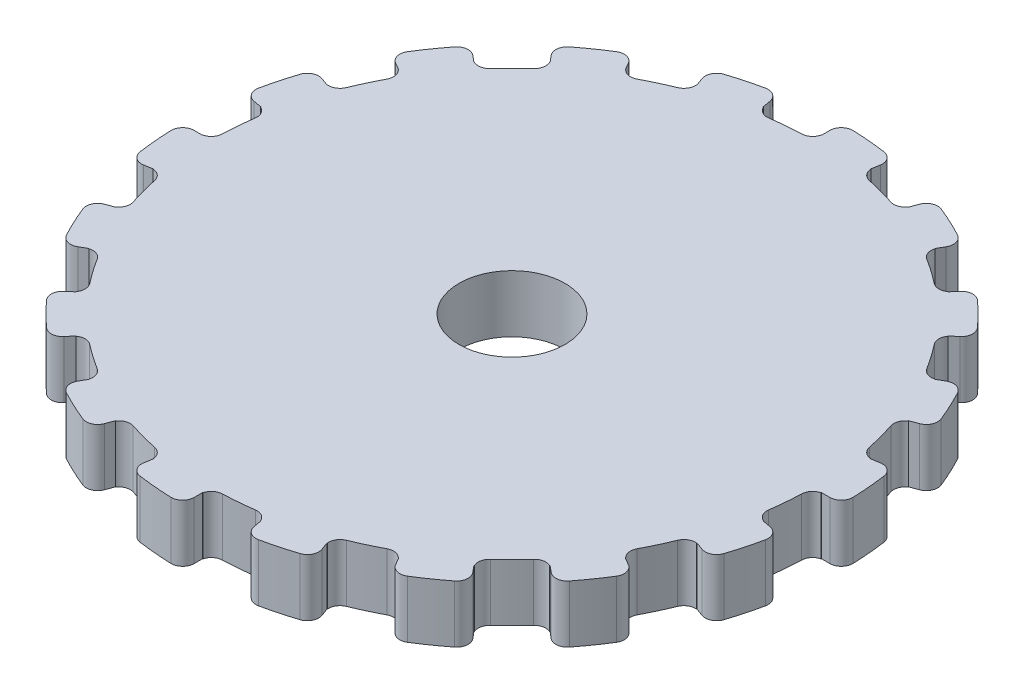
SolidWorks part; units mm, degrees
material "PLA"
ref_plane "Alzado" through (0, 0, 0) normal (0, 0, 1) x (1, 0, 0)
ref_plane "Planta" through (0, 0, 0) normal (0, 1, 0) x (1, 0, 0)
ref_plane "Vista lateral" through (0, 0, 0) normal (1, 0, 0) x (0, 0, -1)
sketch "Croquis1" plane through (0, 0, 0) normal (0, 1, 0) x (1, 0, 0)
  line L0 (0, 0) -> (0, 24) construction
  line L1 (0, 0) -> (4.1676, 23.6354) construction
  line L2 (0, 0) -> (8.2085, 22.5526) construction
  line L3 (0, 0) -> (12, 20.7846) construction
  line L4 (0, 0) -> (15.4269, 18.3851) construction
  line L5 (0, 0) -> (18.3851, 15.4269) construction
  line L6 (0, 0) -> (20.7846, 12) construction
  line L7 (0, 0) -> (22.5526, 8.2085) construction
  line L8 (0, 0) -> (23.6354, 4.1676) construction
  line L9 (0, 0) -> (24, 0) construction
  line L10 (0, 0) -> (23.6354, -4.1676) construction
  line L11 (0, 0) -> (22.5526, -8.2085) construction
  line L12 (0, 0) -> (20.7846, -12) construction
  line L13 (0, 0) -> (18.3851, -15.4269) construction
  line L14 (0, 0) -> (15.4269, -18.3851) construction
  line L15 (0, 0) -> (12, -20.7846) construction
  line L16 (0, 0) -> (8.2085, -22.5526) construction
  line L17 (0, 0) -> (4.1676, -23.6354) construction
  line L18 (0, 0) -> (0, -24) construction
  line L19 (0, 0) -> (-4.1676, -23.6354) construction
  line L20 (0, 0) -> (-8.2085, -22.5526) construction
  line L21 (0, 0) -> (-12, -20.7846) construction
  line L22 (0, 0) -> (-15.4269, -18.3851) construction
  line L23 (0, 0) -> (-18.3851, -15.4269) construction
  line L24 (0, 0) -> (-20.7846, -12) construction
  line L25 (0, 0) -> (-22.5526, -8.2085) construction
  line L26 (0, 0) -> (-23.6354, -4.1676) construction
  line L27 (0, 0) -> (-24, 0) construction
  line L28 (0, 0) -> (-23.6354, 4.1676) construction
  line L29 (0, 0) -> (-22.5526, 8.2085) construction
  line L30 (0, 0) -> (-20.7846, 12) construction
  line L31 (0, 0) -> (-18.3851, 15.4269) construction
  line L32 (0, 0) -> (-15.4269, 18.3851) construction
  line L33 (0, 0) -> (-12, 20.7846) construction
  line L34 (0, 0) -> (-8.2085, 22.5526) construction
  line L35 (0, 0) -> (-4.1676, 23.6354) construction
  line L36 (4.1676, 23.6354) -> (3.7508, 21.2718)
  line L37 (7.3876, 20.2974) -> (8.2085, 22.5526)
  line L38 (12, 20.7846) -> (10.8, 18.7061)
  line L39 (13.8842, 16.5466) -> (15.4269, 18.3851)
  line L40 (18.3851, 15.4269) -> (16.5466, 13.8842)
  line L41 (18.7061, 10.8) -> (20.7846, 12)
  line L42 (22.5526, 8.2085) -> (20.2974, 7.3876)
  line L43 (21.2718, 3.7508) -> (23.6354, 4.1676)
  line L44 (24, 0) -> (21.6, 0)
  line L45 (21.2718, -3.7508) -> (23.6354, -4.1676)
  line L46 (22.5526, -8.2085) -> (20.2974, -7.3876)
  line L47 (18.7061, -10.8) -> (20.7846, -12)
  line L48 (18.3851, -15.4269) -> (16.5466, -13.8842)
  line L49 (13.8842, -16.5466) -> (15.4269, -18.3851)
  line L50 (12, -20.7846) -> (10.8, -18.7061)
  line L51 (7.3876, -20.2974) -> (8.2085, -22.5526)
  line L52 (4.1676, -23.6354) -> (3.7508, -21.2718)
  line L53 (0, -21.6) -> (0, -24)
  line L54 (-4.1676, -23.6354) -> (-3.7508, -21.2718)
  line L55 (-7.3876, -20.2974) -> (-8.2085, -22.5526)
  line L56 (-12, -20.7846) -> (-10.8, -18.7061)
  line L57 (-13.8842, -16.5466) -> (-15.4269, -18.3851)
  line L58 (-18.3851, -15.4269) -> (-16.5466, -13.8842)
  line L59 (-18.7061, -10.8) -> (-20.7846, -12)
  line L60 (-22.5526, -8.2085) -> (-20.2974, -7.3876)
  line L61 (-21.2718, -3.7508) -> (-23.6354, -4.1676)
  line L62 (-24, 0) -> (-21.6, 0)
  line L63 (-21.2718, 3.7508) -> (-23.6354, 4.1676)
  line L64 (-22.5526, 8.2085) -> (-20.2974, 7.3876)
  line L65 (-18.7061, 10.8) -> (-20.7846, 12)
  line L66 (-18.3851, 15.4269) -> (-16.5466, 13.8842)
  line L67 (-13.8842, 16.5466) -> (-15.4269, 18.3851)
  line L68 (-12, 20.7846) -> (-10.8, 18.7061)
  line L69 (-7.3876, 20.2974) -> (-8.2085, 22.5526)
  line L70 (-4.1676, 23.6354) -> (-3.7508, 21.2718)
  line L71 (0, 21.6) -> (0, 24)
  circle A1 centre (0, 0) radius 3.7
  arc A2 (0, 24) -> (4.1676, 23.6354) centre (0, 0) cw
  arc A4 (3.7508, 21.2718) -> (7.3876, 20.2974) centre (0, 0) cw
  arc A5 (8.2085, 22.5526) -> (12, 20.7846) centre (0, 0) cw
  arc A6 (10.8, 18.7061) -> (13.8842, 16.5466) centre (0, 0) cw
  arc A7 (15.4269, 18.3851) -> (18.3851, 15.4269) centre (0, 0) cw
  arc A8 (16.5466, 13.8842) -> (18.7061, 10.8) centre (0, 0) cw
  arc A9 (20.7846, 12) -> (22.5526, 8.2085) centre (0, 0) cw
  arc A10 (20.2974, 7.3876) -> (21.2718, 3.7508) centre (0, 0) cw
  arc A11 (23.6354, 4.1676) -> (24, 0) centre (0, 0) cw
  arc A12 (21.6, 0) -> (21.2718, -3.7508) centre (0, 0) cw
  arc A13 (23.6354, -4.1676) -> (22.5526, -8.2085) centre (0, 0) cw
  arc A14 (20.2974, -7.3876) -> (18.7061, -10.8) centre (0, 0) cw
  arc A15 (20.7846, -12) -> (18.3851, -15.4269) centre (0, 0) cw
  arc A16 (16.5466, -13.8842) -> (13.8842, -16.5466) centre (0, 0) cw
  arc A17 (15.4269, -18.3851) -> (12, -20.7846) centre (0, 0) cw
  arc A18 (10.8, -18.7061) -> (7.3876, -20.2974) centre (0, 0) cw
  arc A19 (8.2085, -22.5526) -> (4.1676, -23.6354) centre (0, 0) cw
  arc A20 (3.7508, -21.2718) -> (0, -21.6) centre (0, 0) cw
  arc A21 (0, -24) -> (-4.1676, -23.6354) centre (0, 0) cw
  arc A22 (-3.7508, -21.2718) -> (-7.3876, -20.2974) centre (0, 0) cw
  arc A23 (-8.2085, -22.5526) -> (-12, -20.7846) centre (0, 0) cw
  arc A24 (-10.8, -18.7061) -> (-13.8842, -16.5466) centre (0, 0) cw
  arc A25 (-15.4269, -18.3851) -> (-18.3851, -15.4269) centre (0, 0) cw
  arc A26 (-16.5466, -13.8842) -> (-18.7061, -10.8) centre (0, 0) cw
  arc A27 (-20.7846, -12) -> (-22.5526, -8.2085) centre (0, 0) cw
  arc A28 (-20.2974, -7.3876) -> (-21.2718, -3.7508) centre (0, 0) cw
  arc A29 (-23.6354, -4.1676) -> (-24, 0) centre (0, 0) cw
  arc A30 (-21.6, 0) -> (-21.2718, 3.7508) centre (0, 0) cw
  arc A31 (-23.6354, 4.1676) -> (-22.5526, 8.2085) centre (0, 0) cw
  arc A32 (-20.2974, 7.3876) -> (-18.7061, 10.8) centre (0, 0) cw
  arc A33 (-20.7846, 12) -> (-18.3851, 15.4269) centre (0, 0) cw
  arc A34 (-16.5466, 13.8842) -> (-13.8842, 16.5466) centre (0, 0) cw
  arc A35 (-15.4269, 18.3851) -> (-12, 20.7846) centre (0, 0) cw
  arc A36 (-10.8, 18.7061) -> (-7.3876, 20.2974) centre (0, 0) cw
  arc A37 (-8.2085, 22.5526) -> (-4.1676, 23.6354) centre (0, 0) cw
  arc A38 (-3.7508, 21.2718) -> (0, 21.6) centre (0, 0) cw
  point P44 (0, 0)
  point P131 (0, 0)
  dimension "D1" = 10
  dimension "D3" = 18
  dimension "D2" = 18
extrude "Saliente-Extruir1" add sketch "Croquis1" along normal blind 4 contours A38 L70 A37 L69 A36 L68 A35 L67 A34 L66 A33 L65 A32 L64 A31 L63 A30 L62 A29 L61 A28 L60 A27 L59 A26 L58 A25 L57 A24 L56 A23 L55 A22 L54 A21 L53 A20 L52 A19 L51 A18 L50 A17 L49 A16 L48 A15 L47 A14 L46 A13 region at (3.2907, 0, -22.5715)
sketch "Croquis2" plane through (0, 4, 0) normal (0, 1, 0) x (1, 0, 0)
  line L0 (0, 1.9) -> (3.1749, 1.9) construction
  line L1 (-2.1, 18.9) -> (2.1, 18.9)
  line L2 (0, 0) -> (0, 1.9) construction
  line L3 (3.1749, 1.9) -> (2.1, 18.9)
  line L4 (0, 18.9) -> (0, 1.9) construction
  line L5 (-3.1749, 1.9) -> (-2.1, 18.9)
  line L6 (-2.178, 0) -> (2.178, 0) construction
  line L7 (3.1749, -1.9) -> (2.1, -18.9)
  line L8 (-2.1, -18.9) -> (2.1, -18.9)
  line L9 (-3.1749, -1.9) -> (-2.1, -18.9)
  circle A0 centre (0, 0) radius 3.7 construction
  arc A1 (3.1749, 1.9) -> (-3.1749, 1.9) centre (0, 0) ccw
  arc A2 (3.1749, -1.9) -> (-3.1749, -1.9) centre (0, 0) cw
sketch "Croquis3" plane through (0, 4, 0) normal (0, 1, 0) x (1, 0, 0)
  line L0 (0, 22.1856) -> (0, 21) construction
  line L1 (3.8525, 21.8485) -> (3.783, 21.4543)
  line L2 (4.1676, 23.6354) -> (3.7508, 21.2718) construction
  line L3 (7.8665, 21.6129) -> (7.451, 20.4715) construction
  line L4 (7.3876, 20.2974) -> (8.2085, 22.5526) construction
  line L5 (7.451, 20.4715) -> (7.5879, 20.8476)
  line L6 (11.0928, 19.2133) -> (10.8927, 18.8666)
  line L7 (14.0033, 16.6885) -> (14.2606, 16.9951)
  line L8 (16.9951, 14.2606) -> (16.6885, 14.0033)
  line L9 (18.8666, 10.8927) -> (19.2133, 11.0928)
  line L10 (20.8476, 7.5879) -> (20.4715, 7.451)
  line L11 (21.4543, 3.783) -> (21.8485, 3.8525)
  line L12 (22.1856, 0) -> (21.7853, 0)
  line L13 (21.4543, -3.783) -> (21.8485, -3.8525)
  line L14 (20.8476, -7.5879) -> (20.4715, -7.451)
  line L15 (18.8666, -10.8927) -> (19.2133, -11.0928)
  line L16 (16.9951, -14.2606) -> (16.6885, -14.0033)
  line L17 (14.0033, -16.6885) -> (14.2606, -16.9951)
  line L18 (11.0928, -19.2133) -> (10.8927, -18.8666)
  line L19 (7.451, -20.4715) -> (7.5879, -20.8476)
  line L20 (3.8525, -21.8485) -> (3.783, -21.4543)
  line L21 (0, -21.7853) -> (0, -22.1856)
  line L22 (-3.8525, -21.8485) -> (-3.783, -21.4543)
  line L23 (-7.451, -20.4715) -> (-7.5879, -20.8476)
  line L24 (-11.0928, -19.2133) -> (-10.8927, -18.8666)
  line L25 (-14.0033, -16.6885) -> (-14.2606, -16.9951)
  line L26 (-16.9951, -14.2606) -> (-16.6885, -14.0033)
  line L27 (-18.8666, -10.8927) -> (-19.2133, -11.0928)
  line L28 (-20.8476, -7.5879) -> (-20.4715, -7.451)
  line L29 (-21.4543, -3.783) -> (-21.8485, -3.8525)
  line L30 (-22.1856, 0) -> (-21.7853, 0)
  line L31 (-21.4543, 3.783) -> (-21.8485, 3.8525)
  line L32 (-20.8476, 7.5879) -> (-20.4715, 7.451)
  line L33 (-18.8666, 10.8927) -> (-19.2133, 11.0928)
  line L34 (-16.9951, 14.2606) -> (-16.6885, 14.0033)
  line L35 (-14.0033, 16.6885) -> (-14.2606, 16.9951)
  line L36 (-11.0928, 19.2133) -> (-10.8927, 18.8666)
  line L37 (-7.451, 20.4715) -> (-7.5879, 20.8476)
  line L38 (-3.8525, 21.8485) -> (-3.783, 21.4543)
  line L39 (0, 21.7853) -> (0, 22.1856)
  line L40 (0, 22.1856) -> (0, 24)
  line L41 (4.1676, 23.6354) -> (3.8525, 21.8485)
  line L42 (7.5879, 20.8476) -> (8.2085, 22.5526)
  line L43 (12, 20.7846) -> (11.0928, 19.2133)
  line L44 (14.2606, 16.9951) -> (15.4269, 18.3851)
  line L45 (18.3851, 15.4269) -> (16.9951, 14.2606)
  line L46 (19.2133, 11.0928) -> (20.7846, 12)
  line L47 (22.5526, 8.2085) -> (20.8476, 7.5879)
  line L48 (21.8485, 3.8525) -> (23.6354, 4.1676)
  line L49 (24, 0) -> (22.1856, 0)
  line L50 (21.8485, -3.8525) -> (23.6354, -4.1676)
  line L51 (22.5526, -8.2085) -> (20.8476, -7.5879)
  line L52 (19.2133, -11.0928) -> (20.7846, -12)
  line L53 (18.3851, -15.4269) -> (16.9951, -14.2606)
  line L54 (14.2606, -16.9951) -> (15.4269, -18.3851)
  line L55 (12, -20.7846) -> (11.0928, -19.2133)
  line L56 (7.5879, -20.8476) -> (8.2085, -22.5526)
  line L57 (4.1676, -23.6354) -> (3.8525, -21.8485)
  line L58 (0, -22.1856) -> (0, -24)
  line L59 (-4.1676, -23.6354) -> (-3.8525, -21.8485)
  line L60 (-7.5879, -20.8476) -> (-8.2085, -22.5526)
  line L61 (-12, -20.7846) -> (-11.0928, -19.2133)
  line L62 (-14.2606, -16.9951) -> (-15.4269, -18.3851)
  line L63 (-18.3851, -15.4269) -> (-16.9951, -14.2606)
  line L64 (-19.2133, -11.0928) -> (-20.7846, -12)
  line L65 (-22.5526, -8.2085) -> (-20.8476, -7.5879)
  line L66 (-21.8485, -3.8525) -> (-23.6354, -4.1676)
  line L67 (-24, 0) -> (-22.1856, 0)
  line L68 (-21.8485, 3.8525) -> (-23.6354, 4.1676)
  line L69 (-22.5526, 8.2085) -> (-20.8476, 7.5879)
  line L70 (-19.2133, 11.0928) -> (-20.7846, 12)
  line L71 (-18.3851, 15.4269) -> (-16.9951, 14.2606)
  line L72 (-14.2606, 16.9951) -> (-15.4269, 18.3851)
  line L73 (-12, 20.7846) -> (-11.0928, 19.2133)
  line L74 (-7.5879, 20.8476) -> (-8.2085, 22.5526)
  line L75 (-4.1676, 23.6354) -> (-3.8525, 21.8485)
  circle A0 centre (0, 0) radius 23 construction
  circle A1 centre (0, 0) radius 21 construction
  arc A2 (0.8288, 22.9851) -> (3.1751, 22.7798) centre (0, 0) cw
  arc A3 (4.4031, 20.5332) -> (6.4534, 19.9838) centre (0, 0) cw
  arc A4 (7.451, 20.4715) -> (6.4534, 19.9838) centre (6.6993, 20.7451) cw
  arc A5 (3.783, 21.4543) -> (4.4031, 20.5332) centre (4.5708, 21.3154) ccw
  arc A6 (3.8525, 21.8485) -> (3.1751, 22.7798) centre (3.0646, 21.9875) ccw
  arc A7 (0, 22.1856) -> (0.8288, 22.9851) centre (0.8, 22.1856) cw
  arc A8 (8.6402, 21.3154) -> (11.506, 19.9151) centre (0, 0) cw construction
  arc A9 (7.5879, 20.8476) -> (8.6402, 21.3154) centre (8.3397, 20.574) cw construction
  arc A10 (7.5879, 20.8476) -> (8.6402, 21.3154) centre (8.3397, 20.574) cw
  arc A11 (8.6402, 21.3154) -> (10.7747, 20.3201) centre (0, 0) cw
  arc A12 (11.0928, 19.2133) -> (10.7747, 20.3201) centre (10.4, 19.6133) ccw
  arc A13 (10.8927, 18.8666) -> (11.1603, 17.789) centre (11.5855, 18.4666) ccw
  arc A14 (11.1603, 17.789) -> (12.8991, 16.5715) centre (0, 0) cw
  arc A15 (14.0033, 16.6885) -> (12.8991, 16.5715) centre (13.3905, 17.2028) cw
  arc A16 (14.2606, 16.9951) -> (15.4094, 17.0748) centre (14.8735, 16.4809) cw
  arc A17 (15.4094, 17.0748) -> (17.0748, 15.4094) centre (0, 0) cw
  arc A18 (16.9951, 14.2606) -> (17.0748, 15.4094) centre (16.4809, 14.8735) ccw
  arc A19 (16.6885, 14.0033) -> (16.5715, 12.8991) centre (17.2028, 13.3905) ccw
  arc A20 (16.5715, 12.8991) -> (17.789, 11.1603) centre (0, 0) cw
  arc A21 (18.8666, 10.8927) -> (17.789, 11.1603) centre (18.4666, 11.5855) cw
  arc A22 (19.2133, 11.0928) -> (20.3201, 10.7747) centre (19.6133, 10.4) cw
  arc A23 (20.3201, 10.7747) -> (21.3154, 8.6402) centre (0, 0) cw
  arc A24 (20.8476, 7.5879) -> (21.3154, 8.6402) centre (20.574, 8.3397) ccw
  arc A25 (20.4715, 7.451) -> (19.9838, 6.4534) centre (20.7451, 6.6993) ccw
  arc A26 (19.9838, 6.4534) -> (20.5332, 4.4031) centre (0, 0) cw
  arc A27 (21.4543, 3.783) -> (20.5332, 4.4031) centre (21.3154, 4.5708) cw
  arc A28 (21.8485, 3.8525) -> (22.7798, 3.1751) centre (21.9875, 3.0646) cw
  arc A29 (22.7798, 3.1751) -> (22.9851, 0.8288) centre (0, 0) cw
  arc A30 (22.1856, 0) -> (22.9851, 0.8288) centre (22.1856, 0.8) ccw
  arc A31 (21.7853, 0) -> (20.9859, -0.7706) centre (21.7853, -0.8) ccw
  arc A32 (20.9859, -0.7706) -> (20.8009, -2.8852) centre (0, 0) cw
  arc A33 (21.4543, -3.783) -> (20.8009, -2.8852) centre (21.5933, -2.9951) cw
  arc A34 (21.8485, -3.8525) -> (22.4919, -4.8076) centre (21.7096, -4.6403) cw
  arc A35 (22.4919, -4.8076) -> (21.8824, -7.0825) centre (0, 0) cw
  arc A36 (20.8476, -7.5879) -> (21.8824, -7.0825) centre (21.1212, -6.8362) ccw
  arc A37 (20.4715, -7.451) -> (19.4567, -7.9018) centre (20.1979, -8.2028) ccw
  arc A38 (19.4567, -7.9018) -> (18.5596, -9.8255) centre (0, 0) cw
  arc A39 (18.8666, -10.8927) -> (18.5596, -9.8255) centre (19.2666, -10.1998) cw
  arc A40 (19.2133, -11.0928) -> (19.4912, -12.2103) centre (18.8133, -11.7856) cw
  arc A41 (19.4912, -12.2103) -> (18.1403, -14.1396) centre (0, 0) cw
  arc A42 (16.9951, -14.2606) -> (18.1403, -14.1396) centre (17.5094, -13.6478) ccw
  arc A43 (16.6885, -14.0033) -> (15.5807, -14.0798) centre (16.1743, -14.6162) ccw
  arc A44 (15.5807, -14.0798) -> (14.0798, -15.5807) centre (0, 0) cw
  arc A45 (14.0033, -16.6885) -> (14.0798, -15.5807) centre (14.6162, -16.1743) cw
  arc A46 (14.2606, -16.9951) -> (14.1396, -18.1403) centre (13.6478, -17.5094) cw
  arc A47 (14.1396, -18.1403) -> (12.2103, -19.4912) centre (0, 0) cw
  arc A48 (11.0928, -19.2133) -> (12.2103, -19.4912) centre (11.7856, -18.8133) ccw
  arc A49 (10.8927, -18.8666) -> (9.8255, -18.5596) centre (10.1998, -19.2666) ccw
  arc A50 (9.8255, -18.5596) -> (7.9018, -19.4567) centre (0, 0) cw
  arc A51 (7.451, -20.4715) -> (7.9018, -19.4567) centre (8.2028, -20.1979) cw
  arc A52 (7.5879, -20.8476) -> (7.0825, -21.8824) centre (6.8362, -21.1212) cw
  arc A53 (7.0825, -21.8824) -> (4.8076, -22.4919) centre (0, 0) cw
  arc A54 (3.8525, -21.8485) -> (4.8076, -22.4919) centre (4.6403, -21.7096) ccw
  arc A55 (3.783, -21.4543) -> (2.8852, -20.8009) centre (2.9951, -21.5933) ccw
  arc A56 (2.8852, -20.8009) -> (0.7706, -20.9859) centre (0, 0) cw
  arc A57 (0, -21.7853) -> (0.7706, -20.9859) centre (0.8, -21.7853) cw
  arc A58 (0, -22.1856) -> (-0.8288, -22.9851) centre (-0.8, -22.1856) cw
  arc A59 (-0.8288, -22.9851) -> (-3.1751, -22.7798) centre (0, 0) cw
  arc A60 (-3.8525, -21.8485) -> (-3.1751, -22.7798) centre (-3.0646, -21.9875) ccw
  arc A61 (-3.783, -21.4543) -> (-4.4031, -20.5332) centre (-4.5708, -21.3154) ccw
  arc A62 (-4.4031, -20.5332) -> (-6.4534, -19.9838) centre (0, 0) cw
  arc A63 (-7.451, -20.4715) -> (-6.4534, -19.9838) centre (-6.6993, -20.7451) cw
  arc A64 (-7.5879, -20.8476) -> (-8.6402, -21.3154) centre (-8.3397, -20.574) cw
  arc A65 (-8.6402, -21.3154) -> (-10.7747, -20.3201) centre (0, 0) cw
  arc A66 (-11.0928, -19.2133) -> (-10.7747, -20.3201) centre (-10.4, -19.6133) ccw
  arc A67 (-10.8927, -18.8666) -> (-11.1603, -17.789) centre (-11.5855, -18.4666) ccw
  arc A68 (-11.1603, -17.789) -> (-12.8991, -16.5715) centre (0, 0) cw
  arc A69 (-14.0033, -16.6885) -> (-12.8991, -16.5715) centre (-13.3905, -17.2028) cw
  arc A70 (-14.2606, -16.9951) -> (-15.4094, -17.0748) centre (-14.8735, -16.4809) cw
  arc A71 (-15.4094, -17.0748) -> (-17.0748, -15.4094) centre (0, 0) cw
  arc A72 (-16.9951, -14.2606) -> (-17.0748, -15.4094) centre (-16.4809, -14.8735) ccw
  arc A73 (-16.6885, -14.0033) -> (-16.5715, -12.8991) centre (-17.2028, -13.3905) ccw
  arc A74 (-16.5715, -12.8991) -> (-17.789, -11.1603) centre (0, 0) cw
  arc A75 (-18.8666, -10.8927) -> (-17.789, -11.1603) centre (-18.4666, -11.5855) cw
  arc A76 (-19.2133, -11.0928) -> (-20.3201, -10.7747) centre (-19.6133, -10.4) cw
  arc A77 (-20.3201, -10.7747) -> (-21.3154, -8.6402) centre (0, 0) cw
  arc A78 (-20.8476, -7.5879) -> (-21.3154, -8.6402) centre (-20.574, -8.3397) ccw
  arc A79 (-20.4715, -7.451) -> (-19.9838, -6.4534) centre (-20.7451, -6.6993) ccw
  arc A80 (-19.9838, -6.4534) -> (-20.5332, -4.4031) centre (0, 0) cw
  arc A81 (-21.4543, -3.783) -> (-20.5332, -4.4031) centre (-21.3154, -4.5708) cw
  arc A82 (-21.8485, -3.8525) -> (-22.7798, -3.1751) centre (-21.9875, -3.0646) cw
  arc A83 (-22.7798, -3.1751) -> (-22.9851, -0.8288) centre (0, 0) cw
  arc A84 (-22.1856, 0) -> (-22.9851, -0.8288) centre (-22.1856, -0.8) ccw
  arc A85 (-21.7853, 0) -> (-20.9859, 0.7706) centre (-21.7853, 0.8) ccw
  arc A86 (-20.9859, 0.7706) -> (-20.8009, 2.8852) centre (0, 0) cw
  arc A87 (-21.4543, 3.783) -> (-20.8009, 2.8852) centre (-21.5933, 2.9951) cw
  arc A88 (-21.8485, 3.8525) -> (-22.4919, 4.8076) centre (-21.7096, 4.6403) cw
  arc A89 (-22.4919, 4.8076) -> (-21.8824, 7.0825) centre (0, 0) cw
  arc A90 (-20.8476, 7.5879) -> (-21.8824, 7.0825) centre (-21.1212, 6.8362) ccw
  arc A91 (-20.4715, 7.451) -> (-19.4567, 7.9018) centre (-20.1979, 8.2028) ccw
  arc A92 (-19.4567, 7.9018) -> (-18.5596, 9.8255) centre (0, 0) cw
  arc A93 (-18.8666, 10.8927) -> (-18.5596, 9.8255) centre (-19.2666, 10.1998) cw
  arc A94 (-19.2133, 11.0928) -> (-19.4912, 12.2103) centre (-18.8133, 11.7856) cw
  arc A95 (-19.4912, 12.2103) -> (-18.1403, 14.1396) centre (0, 0) cw
  arc A96 (-16.9951, 14.2606) -> (-18.1403, 14.1396) centre (-17.5094, 13.6478) ccw
  arc A97 (-16.6885, 14.0033) -> (-15.5807, 14.0798) centre (-16.1743, 14.6162) ccw
  arc A98 (-15.5807, 14.0798) -> (-14.0798, 15.5807) centre (0, 0) cw
  arc A99 (-14.0033, 16.6885) -> (-14.0798, 15.5807) centre (-14.6162, 16.1743) cw
  arc A100 (-14.2606, 16.9951) -> (-14.1396, 18.1403) centre (-13.6478, 17.5094) cw
  arc A101 (-14.1396, 18.1403) -> (-12.2103, 19.4912) centre (0, 0) cw
  arc A102 (-11.0928, 19.2133) -> (-12.2103, 19.4912) centre (-11.7856, 18.8133) ccw
  arc A103 (-10.8927, 18.8666) -> (-9.8255, 18.5596) centre (-10.1998, 19.2666) ccw
  arc A104 (-9.8255, 18.5596) -> (-7.9018, 19.4567) centre (0, 0) cw
  arc A105 (-7.451, 20.4715) -> (-7.9018, 19.4567) centre (-8.2028, 20.1979) cw
  arc A106 (-7.5879, 20.8476) -> (-7.0825, 21.8824) centre (-6.8362, 21.1212) cw
  arc A107 (-7.0825, 21.8824) -> (-4.8076, 22.4919) centre (0, 0) cw
  arc A108 (-3.8525, 21.8485) -> (-4.8076, 22.4919) centre (-4.6403, 21.7096) ccw
  arc A109 (-3.783, 21.4543) -> (-2.8852, 20.8009) centre (-2.9951, 21.5933) ccw
  arc A110 (-2.8852, 20.8009) -> (-0.7706, 20.9859) centre (0, 0) cw
  arc A111 (0, 21.7853) -> (-0.7706, 20.9859) centre (-0.8, 21.7853) cw
  arc A112 (0, 24) -> (4.1676, 23.6354) centre (0, 0) cw
  arc A113 (3.7508, 21.2718) -> (7.3876, 20.2974) centre (0, 0) cw
  arc A114 (8.2085, 22.5526) -> (12, 20.7846) centre (0, 0) cw
  arc A115 (10.8, 18.7061) -> (13.8842, 16.5466) centre (0, 0) cw
  arc A116 (15.4269, 18.3851) -> (18.3851, 15.4269) centre (0, 0) cw
  arc A117 (16.5466, 13.8842) -> (18.7061, 10.8) centre (0, 0) cw
  arc A118 (20.7846, 12) -> (22.5526, 8.2085) centre (0, 0) cw
  arc A119 (20.2974, 7.3876) -> (21.2718, 3.7508) centre (0, 0) cw
  arc A120 (23.6354, 4.1676) -> (24, 0) centre (0, 0) cw
  arc A121 (21.6, 0) -> (21.2718, -3.7508) centre (0, 0) cw
  arc A122 (23.6354, -4.1676) -> (22.5526, -8.2085) centre (0, 0) cw
  arc A123 (20.2974, -7.3876) -> (18.7061, -10.8) centre (0, 0) cw
  arc A124 (20.7846, -12) -> (18.3851, -15.4269) centre (0, 0) cw
  arc A125 (16.5466, -13.8842) -> (13.8842, -16.5466) centre (0, 0) cw
  arc A126 (15.4269, -18.3851) -> (12, -20.7846) centre (0, 0) cw
  arc A127 (10.8, -18.7061) -> (7.3876, -20.2974) centre (0, 0) cw
  arc A128 (8.2085, -22.5526) -> (4.1676, -23.6354) centre (0, 0) cw
  arc A129 (3.7508, -21.2718) -> (0, -21.6) centre (0, 0) cw
  arc A130 (0, -24) -> (-4.1676, -23.6354) centre (0, 0) cw
  arc A131 (-3.7508, -21.2718) -> (-7.3876, -20.2974) centre (0, 0) cw
  arc A132 (-8.2085, -22.5526) -> (-12, -20.7846) centre (0, 0) cw
  arc A133 (-10.8, -18.7061) -> (-13.8842, -16.5466) centre (0, 0) cw
  arc A134 (-15.4269, -18.3851) -> (-18.3851, -15.4269) centre (0, 0) cw
  arc A135 (-16.5466, -13.8842) -> (-18.7061, -10.8) centre (0, 0) cw
  arc A136 (-20.7846, -12) -> (-22.5526, -8.2085) centre (0, 0) cw
  arc A137 (-20.2974, -7.3876) -> (-21.2718, -3.7508) centre (0, 0) cw
  arc A138 (-23.6354, -4.1676) -> (-24, 0) centre (0, 0) cw
  arc A139 (-21.6, 0) -> (-21.2718, 3.7508) centre (0, 0) cw
  arc A140 (-23.6354, 4.1676) -> (-22.5526, 8.2085) centre (0, 0) cw
  arc A141 (-20.2974, 7.3876) -> (-18.7061, 10.8) centre (0, 0) cw
  arc A142 (-20.7846, 12) -> (-18.3851, 15.4269) centre (0, 0) cw
  arc A143 (-16.5466, 13.8842) -> (-13.8842, 16.5466) centre (0, 0) cw
  arc A144 (-15.4269, 18.3851) -> (-12, 20.7846) centre (0, 0) cw
  arc A145 (-10.8, 18.7061) -> (-7.3876, 20.2974) centre (0, 0) cw
  arc A146 (-8.2085, 22.5526) -> (-4.1676, 23.6354) centre (0, 0) cw
  arc A147 (-3.7508, 21.2718) -> (0, 21.6) centre (0, 0) cw
  point P18 (7.1824, 19.7335)
  point P21 (3.6466, 20.681)
  point P24 (3.9939, 22.6506)
  point P27 (0, 23)
  point P257 (0, 0)
  point P369 (0, 0)
  dimension "D1" = 0.8
  dimension "D2" = 0.8
  dimension "D3" = 18
  dimension "D4" = 18
extrude "Cortar-Extruir2" cut sketch "Croquis3" against normal blind 4 contours A112 L40 A7 A2 A6 L41 | A113 A5 A3 A4 region at (2.0417, 4, -23.3365) region at (5.512, 4, -20.5709)
pattern_circular "MatrizC1" count 18 every 20 about axis through (0, 4, 0) along (0, -1, 0) of "Cortar-Extruir2"
scale "Escala1" scale about centroid uniform scaling yes scale factor 0.99
sketch "Croquis4" plane through (0, 3.98, 0) normal (0, 1, 0) x (1, 0, 0)
  point P0 (0, 0)
ref_axis "Eje1" through (0, 0, 0) along (0, 1, 0)
